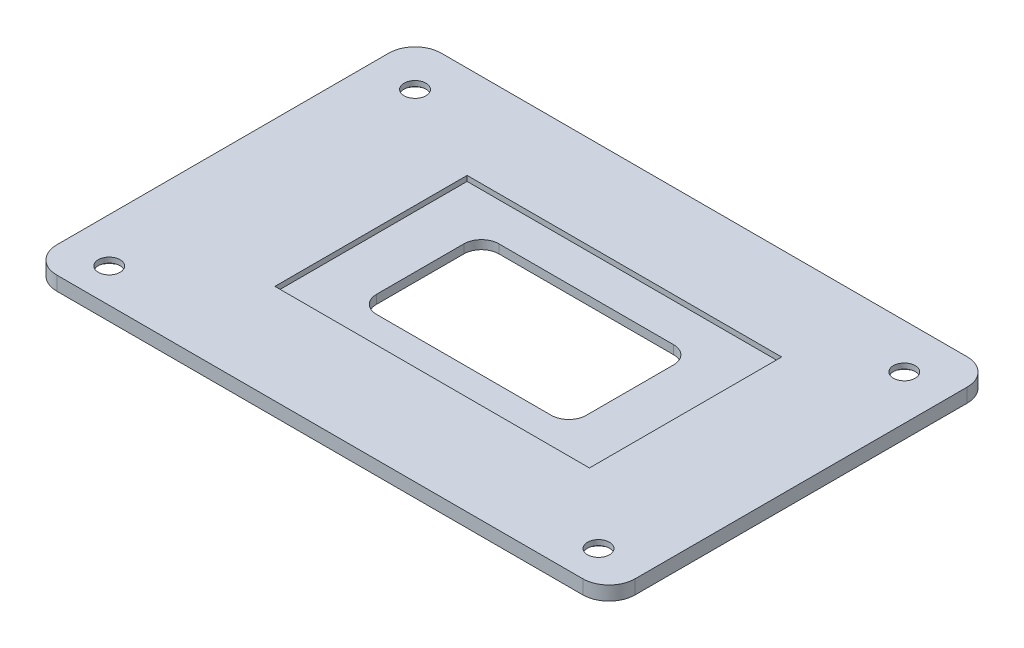
SolidWorks part; units mm, degrees
ref_plane "前视基准面" through (0, 0, 0) normal (0, 0, 1) x (1, 0, 0)
ref_plane "上视基准面" through (0, 0, 0) normal (0, 1, 0) x (1, 0, 0)
ref_plane "右视基准面" through (0, 0, 0) normal (1, 0, 0) x (0, 0, -1)
sketch "草图1" plane through (0, 0, 0) normal (0, 1, 0) x (1, 0, 0)
  line L1 (-30.1, -22) -> (30.1, -22)
  line L2 (-33.1, -19) -> (-33.1, 19)
  line L3 (-30.1, 22) -> (30.1, 22)
  line L4 (33.1, -19) -> (33.1, 19)
  line L5 (-33.1, -22) -> (33.1, 22) construction
  line L6 (-33.1, 22) -> (33.1, -22) construction
  arc A0 (30.1, 22) -> (33.1, 19) centre (30.1, 19) cw
  arc A1 (-33.1, 19) -> (-30.1, 22) centre (-30.1, 19) cw
  arc A2 (30.1, -22) -> (33.1, -19) centre (30.1, -19) ccw
  arc A3 (-30.1, -22) -> (-33.1, -19) centre (-30.1, -19) cw
  point P0 (0, 0)
  dimension "D3" = 3
  dimension "D4" = 3
  dimension "D1" = 44
  dimension "D2" = 66.2
extrude "凸台-拉伸1" add sketch "草图1" along normal blind 1.6
sketch "草图3" plane through (0, 1.6, 0) normal (0, 1, 0) x (1, 0, 0)
  line L0 (-30.1, -22) -> (30.1, -22) construction
  line L1 (-8.5, -7) -> (11.5, -7)
  line L2 (-10.5, -5) -> (-10.5, 5)
  line L3 (-8.5, 7) -> (11.5, 7)
  line L4 (13.5, -5) -> (13.5, 5)
  line L5 (-10.5, -7) -> (13.5, 7) construction
  line L6 (-10.5, 7) -> (13.5, -7) construction
  line L8 (33.1, -19) -> (33.1, 19) construction
  arc A0 (11.5, -7) -> (13.5, -5) centre (11.5, -5) ccw
  arc A1 (-8.5, -7) -> (-10.5, -5) centre (-8.5, -5) cw
  arc A2 (11.5, 7) -> (13.5, 5) centre (11.5, 5) cw
  arc A3 (-10.5, 5) -> (-8.5, 7) centre (-8.5, 5) cw
  point P0 (0, 0)
  dimension "D3" = 2
  dimension "D1" = 24
  dimension "D2" = 14
  dimension "D4" = 19.6
  dimension "D5" = 15
extrude "磁带窗" cut sketch "草图3" against normal up to next
sketch "草图5" plane through (0, 0, 0) normal (0, -1, 0) x (1, 0, 0)
  line L0 (-33.1, -19) -> (-33.1, 19) construction
  line L1 (30.1, -22) -> (-30.1, -22) construction
  circle A0 centre (-28, -16.9) radius 2.6
  circle A1 centre (28, -16.9) radius 2.6
  circle A2 centre (28, 18.1) radius 2.6
  circle A3 centre (-28, 18.1) radius 2.6
  point P0 (-28, -16.9)
  point P10 (28, -16.9)
  point P13 (28, 18.1)
  point P16 (-28, 18.1)
  dimension "D3" = 5.2
  dimension "D1" = 5.1
  dimension "D2" = 5.1
  dimension "D4" = 2
  dimension "D5" = 2
extrude "正螺丝孔" cut sketch "草图5" against normal blind 1
sketch "草图7" plane through (0, 1, 0) normal (0, -1, 0) x (1, 0, 0)
  circle A0 centre (-28, -16.9) radius 1.25
  circle A1 centre (28, -16.9) radius 1.25
  circle A2 centre (28, 18.1) radius 1.25
  circle A3 centre (-28, 18.1) radius 1.25
  dimension "D1" = 2.5
  dimension "D2" = 2
  dimension "D3" = 2
extrude "背螺丝孔" cut sketch "草图7" against normal up to next
sketch "草图9" plane through (0, 1.6, 0) normal (0, 1, 0) x (1, 0, 0)
  line L1 (-16.4991, -10.6372) -> (19.5009, -10.6372)
  line L2 (-16.4991, -10.6372) -> (-16.4991, 11.3628)
  line L3 (-16.4991, 11.3628) -> (19.5009, 11.3628)
  line L4 (19.5009, -10.6372) -> (19.5009, 11.3628)
  line L5 (-16.4991, -10.6372) -> (19.5009, 11.3628) construction
  line L6 (-16.4991, 11.3628) -> (19.5009, -10.6372) construction
  point P0 (1.5009, 0.3628)
  dimension "D1" = 36
  dimension "D2" = 22
extrude "屏幕槽" cut sketch "草图9" against normal blind 0.6 contours L2 L1 L4 L3
